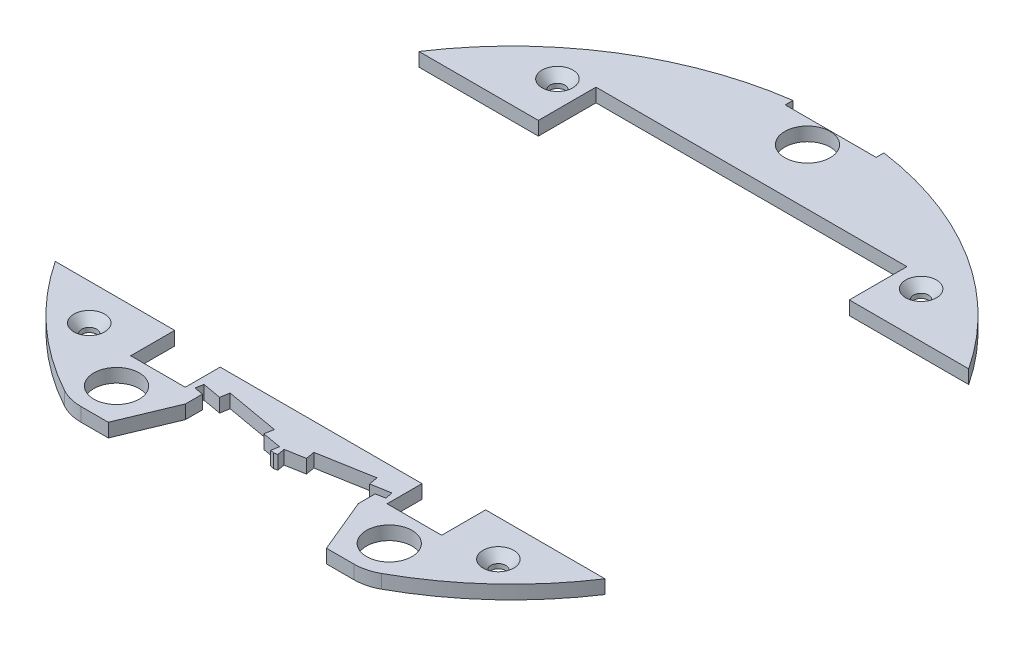
SolidWorks part; units mm, degrees
ref_plane "Front Plane" through (0, 0, 0) normal (0, 0, 1) x (1, 0, 0)
ref_plane "Top Plane" through (0, 0, 0) normal (0, 1, 0) x (1, 0, 0)
ref_plane "Right Plane" through (0, 0, 0) normal (1, 0, 0) x (0, 0, -1)
sketch "Sketch1" plane through (0, 0, 0) normal (0, 1, 0) x (1, 0, 0)
  line L0 (-30.03, -64.8129) -> (30.03, -64.8129)
  line L1 (0, -85) -> (0, 0) construction
  line L2 (0, -85) -> (32.4891, -64.8129) construction
  arc A0 (34.8348, -63.5829) -> (-34.8348, -63.5829) centre (0, 0) ccw
  circle A1 centre (0, -85) radius 38.25 construction
  arc A2 (30.03, -64.8129) -> (34.8348, -63.5829) centre (30.03, -54.8129) ccw
  arc A3 (-30.03, -64.8129) -> (-34.8348, -63.5829) centre (-30.03, -54.8129) cw
  dimension "D1" = 145
  dimension "D2" = 76.5
  dimension "D4" = 10
  dimension "D3" = 85
extrude "Boss-Extrude1" add sketch "Sketch1" along normal blind 3
sketch "Sketch2" plane through (0, 3, 0) normal (0, 1, 0) x (1, 0, 0)
  line L5 (22.2, -49.6757) -> (22.2, -42)
  line L6 (22.2, -42) -> (-22.2, -42)
  line L7 (-22.2, -42) -> (-22.2, -49.6757)
  line L8 (22.2, 49.6757) -> (22.2, 45.5)
  line L9 (-34.2, -49.6757) -> (-22.2, -49.6757) construction
  line L10 (-34.2, -49.6757) -> (-34.2, 49.6757) construction
  line L11 (-34.2, 49.6757) -> (-22.2, 49.6757) construction
  line L19 (34.2, 49.6757) -> (22.2, 49.6757) construction
  line L20 (34.2, -49.6757) -> (34.2, 49.6757) construction
  line L21 (34.2, -49.6757) -> (22.2, -49.6757) construction
  line L22 (22.2, 45.5) -> (-22.2, 45.5)
  line L23 (-22.2, 45.5) -> (-22.2, 49.6757)
  line L35 (-34.2, -49.6757) -> (-22.2, -49.6757)
  line L36 (-34.2, -49.6757) -> (-34.2, 49.6757)
  line L37 (-34.2, 49.6757) -> (-22.2, 49.6757)
  line L55 (34.2, 49.6757) -> (22.2, 49.6757)
  line L56 (34.2, -49.6757) -> (34.2, 49.6757)
  line L57 (34.2, -49.6757) -> (22.2, -49.6757)
  dimension "D1" = 42
  dimension "D2" = 45.5
extrude "Cut-Extrude1" cut sketch "Sketch2" against normal through all contours L55 L37 L36 L35 L7 L6 L5 L57 L56 region at (0, 3, -1.0844)
sketch "Sketch3" plane through (0, 3, 0) normal (0, 1, 0) x (1, 0, 0)
  line L0 (-34.2, 40) -> (-34.2, -40)
  line L1 (-72.5, -40) -> (-34.2, -40)
  line L2 (-72.5, -40) -> (-72.5, 40)
  line L3 (-72.5, 40) -> (-34.2, 40)
  line L4 (72.5, -40) -> (72.5, 40)
  line L5 (-72.5, -40) -> (72.5, 40) construction
  line L6 (-72.5, 40) -> (72.5, -40) construction
  line L7 (-34.2, -49.6757) -> (-34.2, 49.6757) construction
  line L8 (34.2, 40) -> (34.2, -40)
  line L9 (34.2, -49.6757) -> (34.2, 49.6757) construction
  line L10 (34.2, 40) -> (72.5, 40)
  line L11 (34.2, -40) -> (72.5, -40)
  arc A0 (34.8348, -63.5829) -> (-34.8348, -63.5829) centre (0, 0) ccw construction
  point P0 (0, 0)
  dimension "D1" = 80
extrude "Cut-Extrude2" cut sketch "Sketch3" against normal through all
sketch "Sketch4" plane through (0, 3, 0) normal (0, 1, 0) x (1, 0, 0)
  line L0 (-20.9838, -48.7531) -> (-0.7952, -52.3129)
  line L1 (20.9838, -48.7531) -> (20.6886, -47.0789)
  line L2 (0.7952, -52.3129) -> (0.5, -50.6387)
  line L3 (20.6886, -47.0789) -> (0.5, -50.6387)
  line L4 (0, 0) -> (0, -64.8129) construction
  line L5 (-30.03, -64.8129) -> (30.03, -64.8129) construction
  line L6 (-20.6886, -47.0789) -> (-0.5, -50.6387)
  line L7 (-0.7952, -52.3129) -> (-0.5, -50.6387)
  line L8 (-20.9838, -48.7531) -> (-20.6886, -47.0789)
  line L14 (20.9838, -48.7531) -> (0.7952, -52.3129)
  dimension "D1" = 1.7
  dimension "D2" = 20.5
  dimension "D3" = 10
  dimension "D4" = 12.5
  dimension "D5" = 0.5
extrude "Cut-Extrude3" cut sketch "Sketch4" against normal through all
sketch "Sketch5" plane through (0, 3, 0) normal (0, 1, 0) x (1, 0, 0)
  line L0 (-19, -64.8129) -> (-19, -49.1029)
  line L1 (19, -49.1029) -> (0, -52.4531)
  line L2 (0, -52.4531) -> (-19, -49.1029)
  line L3 (-20.9838, -48.7531) -> (-0.7952, -52.3129) construction
  line L4 (0.7952, -52.3129) -> (20.9838, -48.7531) construction
  line L5 (16.5031, -47.8169) -> (4.6854, -49.9007)
  line L6 (16.5031, -47.8169) -> (16.1558, -45.8473)
  line L7 (4.6854, -49.9007) -> (4.3381, -47.9311)
  line L8 (16.1558, -45.8473) -> (4.3381, -47.9311)
  line L9 (20.6886, -47.0789) -> (0.5, -50.6387) construction
  line L10 (0, 0) -> (0, -49.1029) construction
  line L11 (19, -64.8129) -> (19, -49.1029)
  line L13 (-16.1558, -45.8473) -> (-4.3381, -47.9311)
  line L14 (-4.6854, -49.9007) -> (-4.3381, -47.9311)
  line L15 (-16.5031, -47.8169) -> (-16.1558, -45.8473)
  line L16 (-16.5031, -47.8169) -> (-4.6854, -49.9007)
  line L22 (-30.03, -64.8129) -> (30.03, -64.8129) construction
  line L23 (19, -49.1029) -> (-19, -49.1029) construction
  line L25 (-19, -64.8129) -> (19, -64.8129)
  point P14 (10.5943, -48.8588)
  point P15 (10.5943, -48.8588)
  dimension "D1" = 12
  dimension "D2" = 38
  dimension "D4" = 2
extrude "Cut-Extrude4" cut sketch "Sketch5" against normal through all
sketch "Sketch6" plane through (0, 3, 0) normal (0, 1, 0) x (1, 0, 0)
  line L1 (34.2, 49.6757) -> (-34.2, 49.6757)
  line L2 (34.2, 49.6757) -> (34.2, 52.6757)
  line L3 (34.2, 52.6757) -> (-34.2, 52.6757)
  line L4 (-34.2, 49.6757) -> (-34.2, 52.6757)
  dimension "D1" = 3
extrude "Cut-Extrude5" cut sketch "Sketch6" against normal through all body kept at (60.4669, 0, -40)
sketch "Sketch7" plane through (0, 3, 0) normal (0, 1, 0) x (1, 0, 0)
  line L0 (0, 0) -> (0, -31.2827) construction
  circle A0 centre (-30, -57) radius 5
  circle A4 centre (30, -57) radius 5
  dimension "D1" = 10
  dimension "D2" = 30
  dimension "D3" = 57
extrude "Cut-Extrude6" cut sketch "Sketch7" against normal through all
sketch "Sketch11" plane through (0, 3, 0) normal (0, 1, 0) x (1, 0, 0)
  line L0 (0, 0) -> (0, 65) construction
  circle A0 centre (0, 65) radius 5
  dimension "D2" = 10
  dimension "D1" = 65
extrude "Cut-Extrude10" cut sketch "Sketch11" against normal through all
sketch "Sketch13" plane through (0, 3, 0) normal (0, 1, 0) x (1, 0, 0)
  line L0 (19, -52.8129) -> (24, -64.8129)
  line L1 (19, -64.8129) -> (19, -49.1029) construction
  line L2 (19, -64.8129) -> (30.03, -64.8129) construction
  line L3 (24, -64.8129) -> (19, -64.8129)
  line L4 (19, -64.8129) -> (19, -52.8129)
  line L5 (0, 0) -> (0, -25.0729) construction
  line L6 (-19, -64.8129) -> (-19, -52.8129)
  line L7 (-24, -64.8129) -> (-19, -64.8129)
  line L8 (-19, -52.8129) -> (-24, -64.8129)
  dimension "D1" = 12
  dimension "D2" = 5
extrude "Cut-Extrude11" cut sketch "Sketch13" against normal through all
sketch "Sketch14" plane through (0, 3, 0) normal (0, 1, 0) x (1, 0, 0)
  line L1 (0, 0) -> (0, -20.685) construction
  circle A0 centre (45, -48) radius 1.65
  circle A1 centre (-45, -48) radius 1.65
  circle A2 centre (40, 50) radius 1.65
  circle A3 centre (-40, 50) radius 1.65
  dimension "D3" = 3.3
  dimension "D1" = 45
  dimension "D2" = 48
  dimension "D4" = 40
  dimension "D5" = 50
extrude "Cut-Extrude12" cut sketch "Sketch14" against normal through all
sketch "Sketch15" plane through (0, 3, 0) normal (0, 1, 0) x (1, 0, 0)
  line L1 (10, 71.807) -> (-10, 71.807)
  line L2 (10, 71.807) -> (10, 70.107)
  line L3 (10, 70.107) -> (-10, 70.107)
  line L4 (-10, 71.807) -> (-10, 70.107)
  arc A0 (60.4669, 40) -> (-60.4669, 40) centre (0, 0) ccw construction
  dimension "D1" = 20
  dimension "D2" = 1.7
extrude "Cut-Extrude13" cut sketch "Sketch15" against normal blind 10
chamfer "Chamfer1" distance 2 angle 41 2 edges at (-45, 3, 46.35) (45, 3, 49.65) first distance on face at (-45, 0, 46.35) first distance on face at (45, 0, 49.65)
chamfer "Chamfer2" distance 2 angle 41 2 edges at (-40, 3, -51.65) (40, 3, -48.35) first distance on face at (-40, 0, -51.65) first distance on face at (40, 0, -48.35)
equation "\"smallPulleyTeeth\"= 30"
equation "\"largePulleyTeeth\"= 30"
equation "\"eighthThick\"= 3.0mm"
equation "\"sixteenthThick\" = 1.7mm"
equation "\"quarterThick\"=6.0mm"
equation "\"OD\" = 145mm"
equation "\"puckAngle\" = 60.5deg"
equation "\"puckDiam\" = 76.5mm"
equation "\"axlePress\" = 5.9mm"
equation "\"press\" = 0.2mm"
equation "\"wheelClear\" = 0.3mm"
equation "\"10-32clear\" = 4.8mm"
equation "\"6-32clear\" = 3.3mm"
equation "\"8-32clear\" = 4.0mm"
equation "\"4-40clear\" = 3.0mm"
equation "\"wheelHeight\" = 22mm"
equation "\"wheelWell\" = 65mm"
equation "\"D1@Sketch1\"=\"OD\""
equation "\"D1@Boss-Extrude1\"=\"eighthThick\""
equation "\"D2@Sketch1\"=\"puckDiam\""
equation "\"puckDist\" = 85mm"
equation "\"scoopFillet\" = 5mm"
equation "\"10-32tap\" = 4.45mm"
equation "\"ledSmall\" = 3.1mm"
equation "\"ledLarge\" = 4.2mm"
equation "\"ledLength\" = 4.2mm"
equation "\"D3@Sketch1\"=\"puckDist\""
equation "\"D1@Sketch6\"=\"eighthThick\""
equation "\"D2@Sketch15\"=\"sixteenthThick\""
